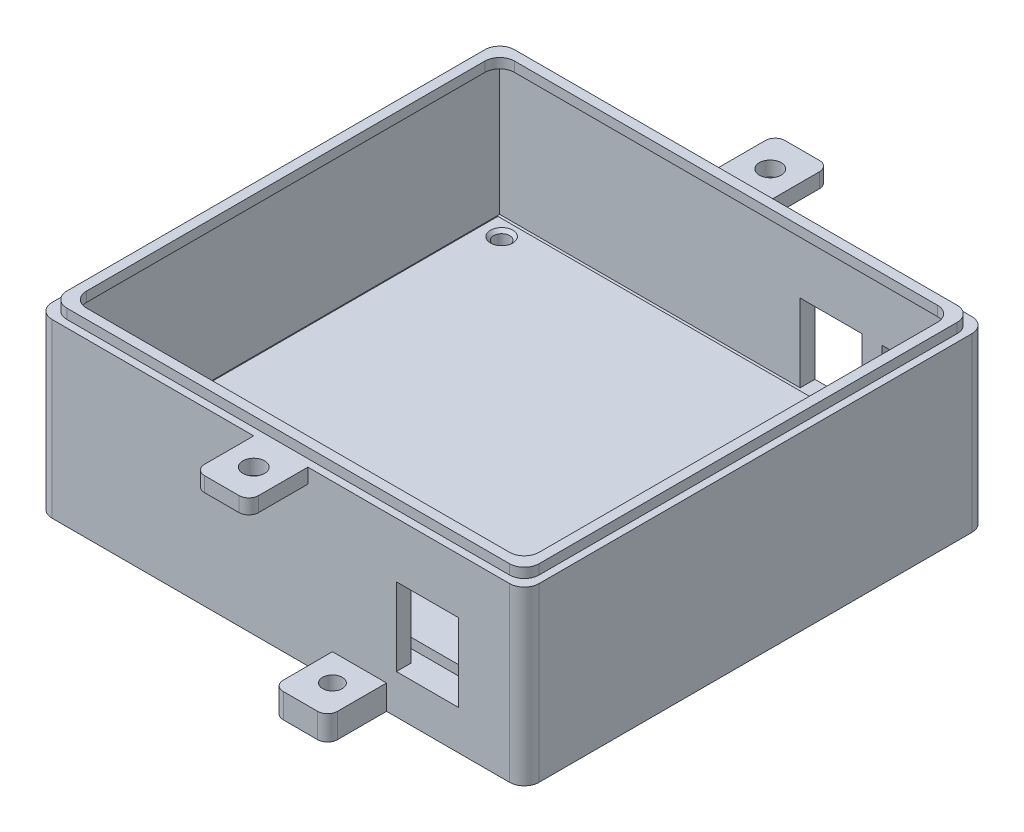
SolidWorks part; units mm, degrees
ref_plane "Plano frontal" through (0, 0, 0) normal (0, 0, 1) x (1, 0, 0)
ref_plane "Plano superior" through (0, 0, 0) normal (0, 1, 0) x (1, 0, 0)
ref_plane "Plano direito" through (0, 0, 0) normal (1, 0, 0) x (0, 0, -1)
sketch "Esboço1" plane through (0, 0, 0) normal (0, 1, 0) x (1, 0, 0)
  line L0 (0, -3) -> (93, -3)
  line L1 (0, 0) -> (93, 0)
  line L2 (0, 0) -> (0, 88)
  line L3 (0, 88) -> (93, 88)
  line L4 (93, 0) -> (93, 88)
  line L5 (-3, 0) -> (-3, 88)
  line L6 (0, 91) -> (93, 91)
  line L7 (96, 0) -> (96, 88)
  line L9 (-3, 38.5) -> (-13, 38.5)
  line L10 (-3, 38.5) -> (-3, 49.5)
  line L11 (-3, 49.5) -> (-13, 49.5)
  line L12 (-15, 40.5) -> (-15, 47.5)
  line L13 (46.5, 88) -> (46.5, 0) construction
  line L15 (0, 44) -> (93, 44) construction
  line L20 (0, 0) -> (93, 88) construction
  line L26 (57, -3) -> (68, -3)
  line L27 (57, -3) -> (57, -13)
  line L28 (59, -15) -> (66, -15)
  line L29 (68, -3) -> (68, -13)
  arc A3 (93, -3) -> (96, 0) centre (93, 0) ccw
  arc A4 (93, 91) -> (96, 88) centre (93, 88) cw
  arc A5 (-3, 88) -> (0, 91) centre (0, 88) cw
  arc A6 (0, -3) -> (-3, 0) centre (0, 0) cw
  arc A7 (-13, 38.5) -> (-15, 40.5) centre (-13, 40.5) cw
  arc A8 (-13, 49.5) -> (-15, 47.5) centre (-13, 47.5) ccw
  circle A9 centre (-8.5, 44) radius 2
  arc A16 (66, -15) -> (68, -13) centre (66, -13) ccw
  arc A17 (57, -13) -> (59, -15) centre (59, -13) ccw
  circle A18 centre (62.5, -8.5) radius 2
  point P15 (96, -3)
  point P24 (96, 91)
  point P35 (0, 0)
  dimension "D10" = 2
  dimension "D7" = 38.5
  dimension "D8" = 3
  dimension "D11" = 10
  dimension "D14" = 2
  dimension "D15" = 10
  dimension "D1" = 93
  dimension "D2" = 88
  dimension "D3" = 99
  dimension "D4" = 94
  dimension "D5" = 3
  dimension "D6" = 3
  dimension "D9" = 38.5
  dimension "D12" = 5.5
  dimension "D13" = 5.5
  dimension "D16" = 5.5
  dimension "D17" = 11
  dimension "D18" = 5.5
  dimension "D19" = 25
extrude "Ressalto-extrusão2" add sketch "Esboço1" along normal blind 35 contours L0 L7 L6 L5 L4 L1 L2 L3 region at (-1.156, 0, 1.156)
extrude "Ressalto-extrusão3" add sketch "Esboço1<5>" along normal blind 8 contours L1 L4 L3 L2 region at (46.5, 0, -44)
sketch "Esboço1<5>" plane through (0, 0, 0) normal (0, 1, 0) x (1, 0, 0) same geometry as "Esboço1"
extrude "Ressalto-extrusão6" add sketch "Esboço1<7>" along normal blind 5 contours L11 A8 L12 A7 L9 L5 A9 | L7 | A17 L28 A16 L29 L26 L27 | A18 region at (-8, 0, -38.6628)
sketch "Esboço1<7>" plane through (0, 0, 0) normal (0, 1, 0) x (1, 0, 0) same geometry as "Esboço1"
sketch "Esboço4" plane through (0, 35, 0) normal (0, 1, 0) x (1, 0, 0)
  line L0 (0, -3) -> (93, -3) construction
  line L1 (41, -3) -> (52, -3)
  line L2 (41, -3) -> (41, -13)
  line L3 (43, -15) -> (50, -15)
  line L4 (52, -3) -> (52, -13)
  line L6 (0, 44) -> (93, 44) construction
  line L7 (0, 0) -> (0, 88) construction
  line L8 (93, 0) -> (93, 88) construction
  line L9 (43, 103) -> (50, 103)
  line L10 (52, 91) -> (52, 101)
  line L11 (41, 91) -> (52, 91)
  line L12 (41, 91) -> (41, 101)
  arc A0 (50, -15) -> (52, -13) centre (50, -13) ccw
  arc A1 (41, -13) -> (43, -15) centre (43, -13) ccw
  circle A2 centre (46.5, -8.5) radius 2.2186
  circle A3 centre (46.5, 96.5) radius 2.2186
  arc A4 (50, 103) -> (52, 101) centre (50, 101) cw
  arc A5 (41, 101) -> (43, 103) centre (43, 101) cw
  dimension "D3" = 2
  dimension "D1" = 41
  dimension "D2" = 41
  dimension "D4" = 10
  dimension "D5" = 5.5
  dimension "D6" = 5.5
extrude "Ressalto-extrusão7" add sketch "Esboço4" against normal blind 3
sketch "Esboço5" plane through (0, 8, 0) normal (0, 1, 0) x (1, 0, 0)
  line L0 (0, 0) -> (0, 88) construction
  line L1 (2.175, 85.46) -> (90.825, 85.46)
  line L2 (2.175, 85.46) -> (2.175, 2.54)
  line L3 (2.175, 2.54) -> (90.825, 2.54)
  line L4 (90.825, 85.46) -> (90.825, 2.54)
  line L5 (93, 0) -> (93, 88) construction
  line L6 (0, 88) -> (93, 88) construction
  line L7 (0, 0) -> (93, 0) construction
  dimension "D1" = 2.175
  dimension "D2" = 2.175
  dimension "D3" = 2.54
  dimension "D4" = 2.54
extrude "Ressalto-extrusão8" add sketch "Esboço5" along normal blind 2
sketch "Esboço7" plane through (0, 0, -88) normal (0, 0, 1) x (1, 0, 0)
  line L0 (90.825, 8) -> (2.175, 8) construction
  line L1 (61.08, 23.81) -> (73.68, 23.81)
  line L2 (61.08, 23.81) -> (61.08, 8)
  line L3 (61.08, 8) -> (73.68, 8)
  line L4 (73.68, 23.81) -> (73.68, 8)
  line L5 (0, 35) -> (0, 0) construction
  line L9 (0, 35) -> (93, 35) construction
  line L10 (77.72, 23.81) -> (90.32, 23.81)
  line L11 (77.72, 23.81) -> (77.72, 8)
  line L12 (77.72, 8) -> (90.32, 8)
  line L13 (90.32, 23.81) -> (90.32, 8)
  line L14 (0, 8) -> (93, 8) construction
  dimension "D1" = 61.08
  dimension "D2" = 12.6
  dimension "D3" = 15.81
  dimension "D4" = 11.19
  dimension "D5" = 4.04
  dimension "D6" = 0
  dimension "D7" = 0
extrude "Corte-extrusão1" cut sketch "Esboço7" against normal through all
sketch "Esboço8" plane through (0, 0, 0) normal (0, 0, -1) x (-1, 0, 0)
  line L0 (-2.175, 8) -> (-90.825, 8) construction
  line L1 (-82.59, 23.81) -> (-69.99, 23.81)
  line L2 (-82.59, 23.81) -> (-82.59, 8)
  line L3 (-82.59, 8) -> (-69.99, 8)
  line L4 (-69.99, 23.81) -> (-69.99, 8)
  line L5 (-93, 35) -> (-93, 8) construction
  line L8 (0, 35) -> (-93, 35) construction
  dimension "D1" = 10.41
  dimension "D2" = 11.19
  dimension "D3" = 15.81
  dimension "D4" = 12.6
extrude "Corte-extrusão2" cut sketch "Esboço8" against normal through all
sketch "Esboço9" plane through (0, 10, 0) normal (0, 1, 0) x (1, 0, 0)
  line L0 (0, 0) -> (0, 88) construction
  line L3 (0, 88) -> (61.08, 88) construction
  line L5 (0, 0) -> (69.99, 0) construction
  line L6 (93, 0) -> (93, 88) construction
  line L7 (82.59, 0) -> (93, 0) construction
  circle A0 centre (6.12, 82.28) radius 2
  circle A1 centre (6.12, 5.83) radius 2
  circle A2 centre (86.89, 5.83) radius 2
  dimension "D1" = 6.12
  dimension "D2" = 5.72
  dimension "D3" = 6.12
  dimension "D4" = 5.83
  dimension "D5" = 6.11
  dimension "D6" = 5.83
hole_wizard "Furo com folga de #41" positions "3DSketch1" profile "Esboço10" hole size "#4" standard "Ansi Inch"
sketch3d "3DSketch1"
  point P0 (6.12, 10, -82.28)
  point P3 (6.12, 10, -5.83)
  point P6 (86.89, 10, -5.83)
sketch "Esboço10" plane through (6.12, 10, -82.28) normal (1, 0, 0) x (0, 0, 1)
  line L0 (0, 0) -> (0, 8.9806)
  line L1 (0, 8.9806) -> (1.6319, 8)
  line L2 (1.6319, 8) -> (1.6319, 0.635)
  line L3 (1.6319, 0.635) -> (2.2669, 0)
  line L5 (2.2669, 0) -> (0, 0)
  line L6 (-1.6319, 0.635) -> (-2.2669, 0) construction
  line L10 (0, 8.9806) -> (-1.632, 8) construction
  line L11 (0, -6.35) -> (0, 107.95) construction
  dimension "Hole Dia." = 3.2639
  dimension "Hole Depth" = 8
  dimension "Near C'Sink Dia." = 4.5339
  dimension "Near C'Sink Angle" = 90
  dimension "Drill Angle" = 118
sketch "Esboço14" plane through (0, 35, 0) normal (0, 1, 0) x (1, 0, 0)
  line L0 (-3, 0) -> (-3, 88) construction
  line L1 (1.5, 89.5) -> (91.5, 89.5)
  line L2 (-1.5, 86.5) -> (-1.5, 1.5)
  line L3 (1.5, -1.5) -> (91.5, -1.5)
  line L4 (94.5, 86.5) -> (94.5, 1.5)
  line L5 (0, 91) -> (41, 91) construction
  line L6 (96, 0) -> (96, 88) construction
  line L7 (52, -3) -> (93, -3) construction
  line L9 (3.5, 87.5) -> (89.5, 87.5)
  line L10 (0.5, 84.5) -> (0.5, 3.5)
  line L11 (3.5, 0.5) -> (89.5, 0.5)
  line L12 (92.5, 84.5) -> (92.5, 3.5)
  arc A0 (91.5, 89.5) -> (94.5, 86.5) centre (91.5, 86.5) cw
  arc A1 (91.5, -1.5) -> (94.5, 1.5) centre (91.5, 1.5) ccw
  arc A2 (-1.5, 1.5) -> (1.5, -1.5) centre (1.5, 1.5) ccw
  arc A3 (1.5, 89.5) -> (-1.5, 86.5) centre (1.5, 86.5) ccw
  arc A4 (89.5, 87.5) -> (92.5, 84.5) centre (89.5, 84.5) cw
  arc A5 (89.5, 0.5) -> (92.5, 3.5) centre (89.5, 3.5) ccw
  arc A6 (0.5, 3.5) -> (3.5, 0.5) centre (3.5, 3.5) ccw
  arc A7 (3.5, 87.5) -> (0.5, 84.5) centre (3.5, 84.5) ccw
  dimension "D5" = 3
  dimension "D10" = 3
  dimension "D1" = 1.5
  dimension "D2" = 1.5
  dimension "D3" = 1.5
  dimension "D4" = 1.5
  dimension "D6" = 2
  dimension "D7" = 2
  dimension "D8" = 2
  dimension "D9" = 2
extrude "Ressalto-extrusão10" add sketch "Esboço14" along normal blind 2
